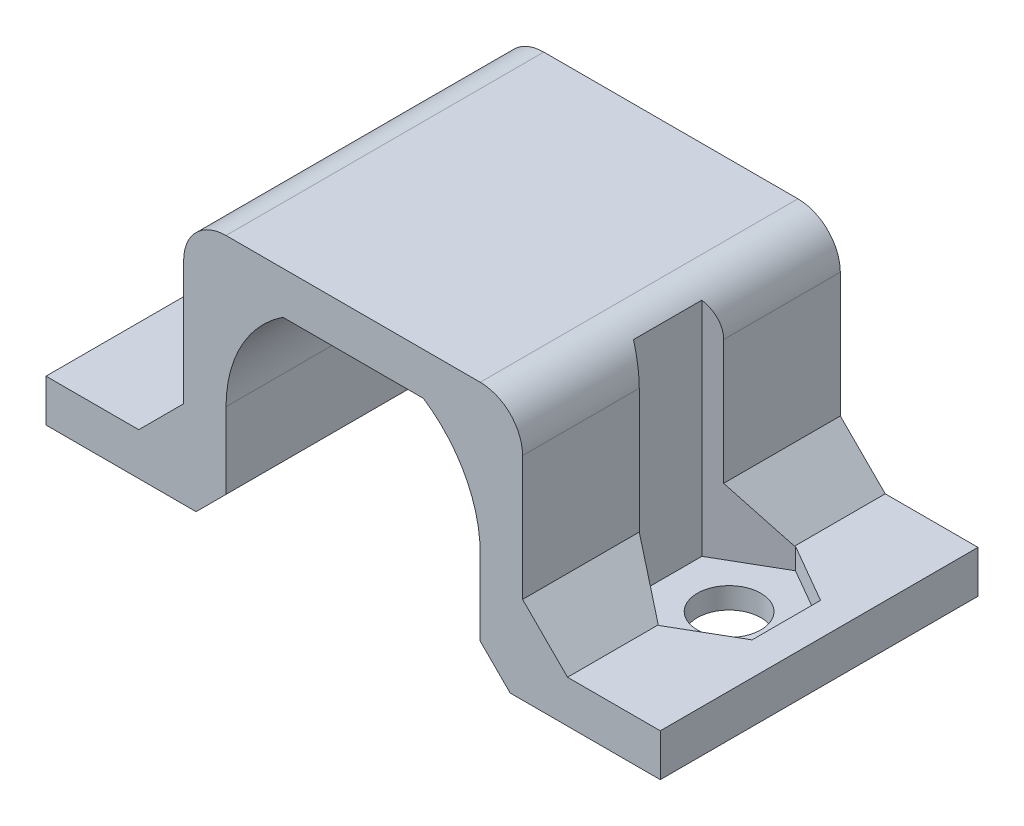
SolidWorks part; units mm, degrees
material "ABS"
ref_plane "Alzado" through (0, 0, 0) normal (0, 0, 1) x (1, 0, 0)
ref_plane "Planta" through (0, 0, 0) normal (0, 1, 0) x (1, 0, 0)
ref_plane "Vista lateral" through (0, 0, 0) normal (1, 0, 0) x (0, 0, -1)
sketch "Croquis1" plane through (0, 0, 0) normal (0, 0, 1) x (1, 0, 0)
  line L0 (14.5, 0) -> (7.4142, 0)
  line L1 (7.4142, 0) -> (6, 1.4142)
  line L2 (6, 1.4142) -> (6, 5)
  line L3 (3.3166, 10) -> (-3.3166, 10)
  line L4 (-8, 12) -> (8, 12)
  line L5 (8, 12) -> (8, 4.1213)
  line L6 (8, 4.1213) -> (10.1213, 2)
  line L7 (10.1213, 2) -> (14.5, 2)
  line L8 (14.5, 2) -> (14.5, 0)
  line L10 (0, 0) -> (0, 50000) construction
  line L12 (-14.5, 2) -> (-14.5, 0)
  line L13 (-10.1213, 2) -> (-14.5, 2)
  line L14 (-8, 4.1213) -> (-10.1213, 2)
  line L15 (-8, 12) -> (-8, 4.1213)
  line L16 (-6, 1.4142) -> (-6, 5)
  line L17 (-7.4142, 0) -> (-6, 1.4142)
  line L18 (-14.5, 0) -> (-7.4142, 0)
  arc A0 (6, 5) -> (3.3166, 10) centre (0, 5) ccw
  arc A3 (-6, 5) -> (-3.3166, 10) centre (0, 5) cw
  point P7 (0, 10)
  point P29 (0, 12)
  dimension "D10" = 3
  dimension "D1" = 12
  dimension "D2" = 10
  dimension "D3" = 2
  dimension "D4" = 2
  dimension "D5" = 45
  dimension "D6" = 2
  dimension "D7" = 2
  dimension "D8" = 8.5
  dimension "D9" = 5
extrude "Saliente-Extruir1" add sketch "Croquis1" along normal mid plane 15
fillet "Redondeo1" radius 2 2 edges at (-8, 12, 0) (8, 12, 0)
sketch "Croquis3" plane through (0, 12, 0) normal (0, 1, 0) x (1, 0, 0)
  line L0 (0, 0) -> (0, 9.6966) construction
  line L1 (-10.15, -3.2332) -> (-7.35, -1.6166)
  line L2 (-7.35, -1.6166) -> (-7.35, 1.6166)
  line L3 (-7.35, 1.6166) -> (-10.15, 3.2332)
  line L4 (-10.15, 3.2332) -> (-12.95, 1.6166)
  line L5 (-12.95, 1.6166) -> (-12.95, -1.6166)
  line L6 (-12.95, -1.6166) -> (-10.15, -3.2332)
  line L7 (12.95, -1.6166) -> (10.15, -3.2332)
  line L8 (12.95, 1.6166) -> (12.95, -1.6166)
  line L9 (10.15, 3.2332) -> (12.95, 1.6166)
  line L10 (7.35, 1.6166) -> (10.15, 3.2332)
  line L11 (7.35, -1.6166) -> (7.35, 1.6166)
  line L12 (10.15, -3.2332) -> (7.35, -1.6166)
  line L13 (-14.5, -7.5) -> (-14.5, 7.5) construction
  circle A0 centre (-10.15, 0) radius 2.8 construction
  circle A1 centre (10.15, 0) radius 2.8 construction
  dimension "D1" = 5.6
  dimension "D2" = 1.55
extrude "Cortar-Extruir2" cut sketch "Croquis3" against normal blind 11
sketch "Croquis4" plane through (0, 0, 0) normal (0, -1, 0) x (1, 0, 0)
  line L0 (0, 0) -> (0, 8.3958) construction
  line L1 (-14.5, 7.5) -> (-14.5, -7.5) construction
  circle A0 centre (-10.25, 0) radius 1.5
  circle A1 centre (10.25, 0) radius 1.5
  dimension "D1" = 3
  dimension "D2" = 4.25
extrude "Cortar-Extruir3" cut sketch "Croquis4" against normal blind 11
